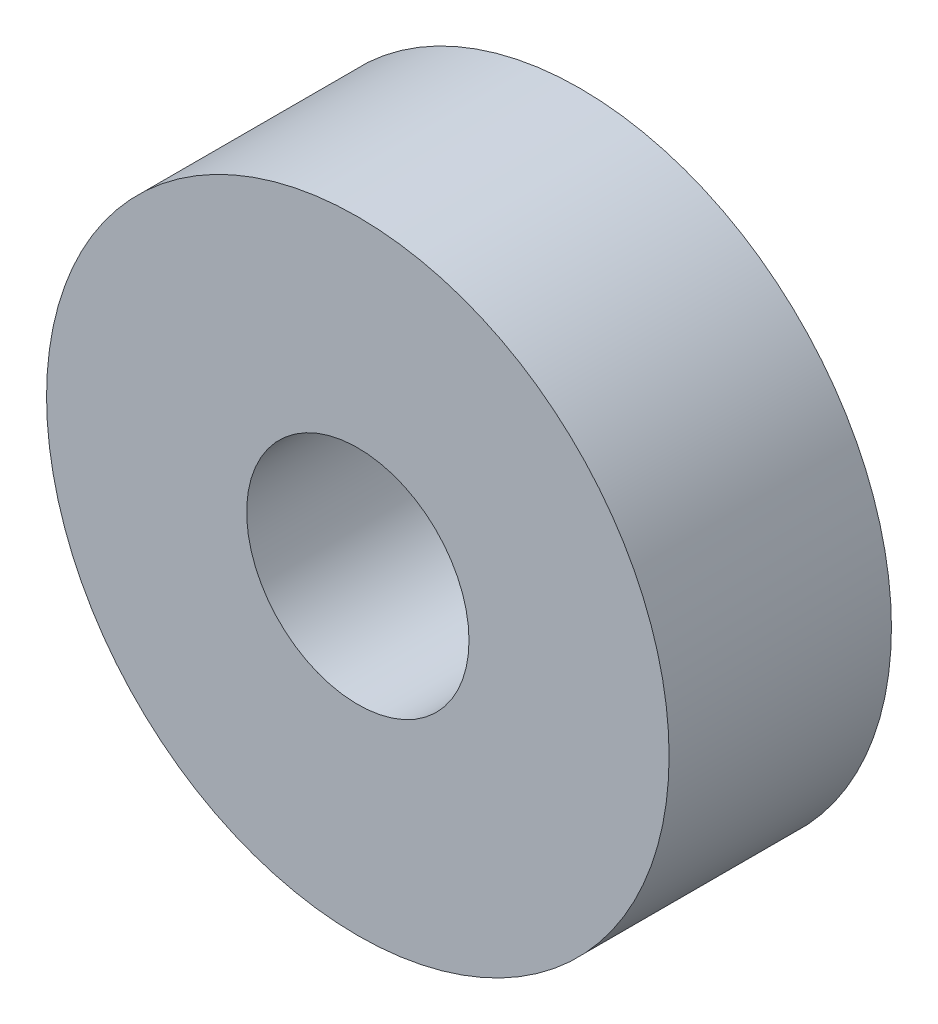
SolidWorks part; units mm, degrees
ref_plane "Front Plane" through (0, 0, 0) normal (0, 0, 1) x (1, 0, 0)
ref_plane "Top Plane" through (0, 0, 0) normal (0, 1, 0) x (1, 0, 0)
ref_plane "Right Plane" through (0, 0, 0) normal (1, 0, 0) x (0, 0, -1)
ref_plane "Plane1" through (0, 0, 5) normal (0, 0, 1) x (1, 0, 0)
sketch "Sketch1" plane through (0, 0, 5) normal (0, 0, 1) x (1, 0, 0)
  circle A0 centre (0, 0) radius 7
extrude "Boss-Extrude1" add sketch "Sketch1" against normal blind 5
hole_wizard "Ø5.0 (5) Diameter Hole1" positions "Sketch3" profile "Sketch2" hole size "Ø5.0" standard "ANSI Metric"
sketch "Sketch3" plane through (0, 0, 5) normal (0, 0, 1) x (1, 0, 0)
  point P0 (0, 0)
sketch "Sketch2" plane through (0, 0, 5) normal (1, 0, 0) x (0, -1, 0)
  line L0 (0, 0) -> (0, 5)
  line L1 (0, 5) -> (2.5, 5)
  line L2 (2.5, 5) -> (2.5, 0)
  line L5 (2.5, 0) -> (0, 0)
  line L11 (0, -6.35) -> (0, 107.95) construction
  dimension "Thru Hole Dia." = 5
  dimension "Thru Hole Depth" = 5
ref_axis "Axis1" through (0, 0, -1.6909) along (0, 0, 1)
